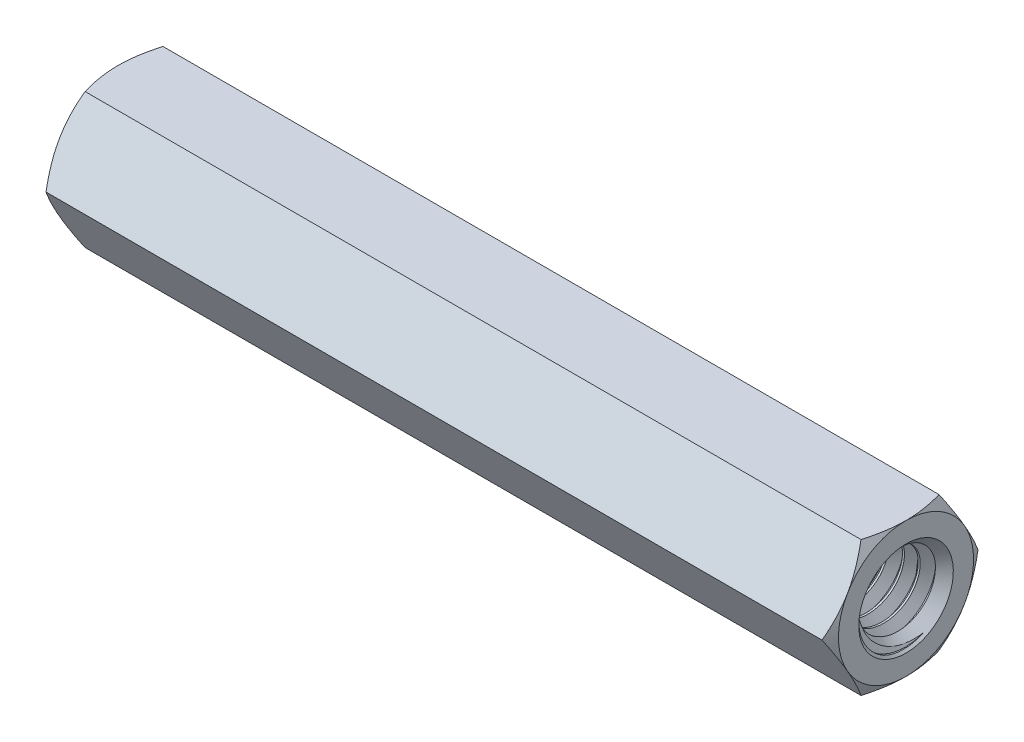
SolidWorks part; units mm, degrees
note: '?' marks a value the reader was unsure of.
material "6061 Alloy"
ref_plane "Front Plane" through (0, 0, 0) normal (0, 0, 1) x (1, 0, 0)
ref_plane "Top Plane" through (0, 0, 0) normal (0, 1, 0) x (1, 0, 0)
ref_plane "Right Plane" through (0, 0, 0) normal (1, 0, 0) x (0, 0, -1)
sketch "Sketch1" plane through (0, 0, 0) normal (0, 0, 1) x (1, 0, 0)
  line L0 (0, 0) -> (35, 0) construction
  line L1 (0, 3) -> (0, -3) construction
  line L2 (0, 2) -> (11, 2) construction
  line L3 (0, 2) -> (-0.7, 2) construction
  line L4 (0, 3) -> (35, 3) construction
  point P6 (0, 0)
  dimension "Hex" = 6
  dimension "Pitch" = 0.7
  dimension "Thread Length" = 11
  dimension "Thread OD" = 4
  dimension "Length" = 35
sketch "Sketch2" plane through (0, 0, 0) normal (1, 0, 0) x (0, 0, -1)
  line L0 (0, 0) -> (-1.4142, -1.4142) construction
  line L1 (1.7321, 3) -> (-1.7321, 3)
  line L2 (-1.7321, 3) -> (-3.4641, 0)
  line L3 (-3.4641, 0) -> (-1.7321, -3)
  line L4 (-1.7321, -3) -> (1.7321, -3)
  line L5 (1.7321, -3) -> (3.4641, 0)
  line L6 (3.4641, 0) -> (1.7321, 3)
  circle A0 centre (0, 0) radius 3 construction
  circle A1 centre (0, 0) radius 2 construction
  dimension "D1" = 45
extrude "Boss-Extrude1" add sketch "Sketch2" along normal up to vertex (35 mm away) up to point (35, 0, 0)
sketch "Sketch3" plane through (0, 0, 0) normal (0, 0, 1) x (1, 0, 0)
  line L0 (0, 2.1) -> (0.1, 2)
  line L1 (0, 0) -> (11, 0)
  line L2 (0, 0) -> (0, 2.1)
  line L3 (0.1, 2) -> (11, 2)
  line L4 (11, 0) -> (11, 2)
  line L5 (35, 0) -> (24, 0)
  line L8 (24, 0) -> (24, 2)
  line L9 (0, 3) -> (0, -3) construction
  line L13 (0, 0) -> (35, 0) construction
  line L14 (24, 2) -> (34.9, 2)
  line L15 (34.9, 2) -> (35, 2.1)
  line L16 (35, 3) -> (35, 0) construction
  line L17 (35, 2.1) -> (35, 0)
  dimension "D1" = 4.2
  dimension "D2" = 45
revolve "Cut-Revolve1" cut sketch "Sketch3" angle 360 about L13
sketch "Sketch4" plane through (0, 0, 0) normal (-1, 0, 0) x (0, 0, 1)
  circle A0 centre (0, 0) radius 3
  circle A1 centre (0, 0) radius 3 construction
extrude "Cut-Extrude1" cut sketch "Sketch4" against normal through all draft 60 flip side to cut
sketch "Sketch5" plane through (35, 0, 0) normal (1, 0, 0) x (0, 0, -1)
  circle A0 centre (0, 0) radius 3
  circle A1 centre (0, 0) radius 3 construction
extrude "Cut-Extrude2" cut sketch "Sketch5" against normal through all draft 60 flip side to cut
ref_axis "Center Axis 1" through (0, 0, 0) along (1, 0, 0)?
sketch "Sketch6" plane through (0, 0, 0) normal (0, 0, 1) x (1, 0, 0)
  line L0 (-0.599, 2) -> (-0.2995, 1.4813) construction
  line L1 (-0.2995, 1.4813) -> (0, 2) construction
  line L2 (0, 2) -> (-0.599, 2) construction
  line L3 (0, 2) -> (-0.7, 2) construction
  line L5 (-0.599, 2) -> (-0.6495, 2.0875) construction
  line L6 (-0.6495, 2.0875) -> (0.0505, 2.0875) construction
  line L7 (0.0505, 2.0875) -> (0, 2) construction
  line L8 (-0.3432, 1.5571) -> (-0.2557, 1.5571) construction
  line L9 (-0.2995, 2) -> (-0.2995, 2.0875) construction
  line L10 (-0.6242, 2.0438) -> (0.0253, 2.0438)
  line L11 (0.0253, 2.0438) -> (-0.2557, 1.5571)
  line L12 (-0.2557, 1.5571) -> (-0.3432, 1.5571)
  line L13 (-0.3432, 1.5571) -> (-0.6242, 2.0438)
  dimension "D1" = 0.0875
sketch "Sketch7" plane through (0, 0, 0) normal (-1, 0, 0) x (0, 0, 1)
  line L0 (0, 3) -> (0, -3) construction
  circle A0 centre (0, 0) radius 2
curve "Helix/Spiral1" pitch 0.7 height 11.7 turns 16.7143
sweep "Sweep1" add profiles "Sketch6" path "Helix/Spiral1"
pattern_linear "LPattern1" count 2 spacing 24 along (1, 0, 0) of "Sweep1"
combine bodies "Combine1" operation type add bodies to combine 107 108 109
sketch "Sketch8" plane through (0, 0, 0) normal (-1, 0, 0) x (0, 0, 1)
  circle A0 centre (0, 0) radius 2.1
extrude "Cut-Extrude3" cut sketch "Sketch8" against normal through all draft 45 and the other way through all draft 45
sketch "Sketch9" plane through (35, 0, 0) normal (1, 0, 0) x (0, 0, -1)
  circle A0 centre (0, 0) radius 2.1
  circle A1 centre (0, 0) radius 2.1 construction
extrude "Cut-Extrude4" cut sketch "Sketch9" against normal through all draft 45 and the other way through all draft 45
ref_axis "Axis1" through (-1.9887, 0, 0) along (1, 0, 0)?
equation "\"D1@Sketch3\"=\"Thread OD@Sketch1\"*1.05"
equation "\"D1@Sketch6\"=\"Pitch@Sketch1\"/8"
equation "\"D4@Helix/Spiral1\"=\"Pitch@Sketch1\""
equation "\"D3@Helix/Spiral1\"=\"Pitch@Sketch1\"+\"Thread Length@Sketch1\""
equation "\"D3@LPattern1\"=\"Length@Sketch1\"-\"Thread Length@Sketch1\""
